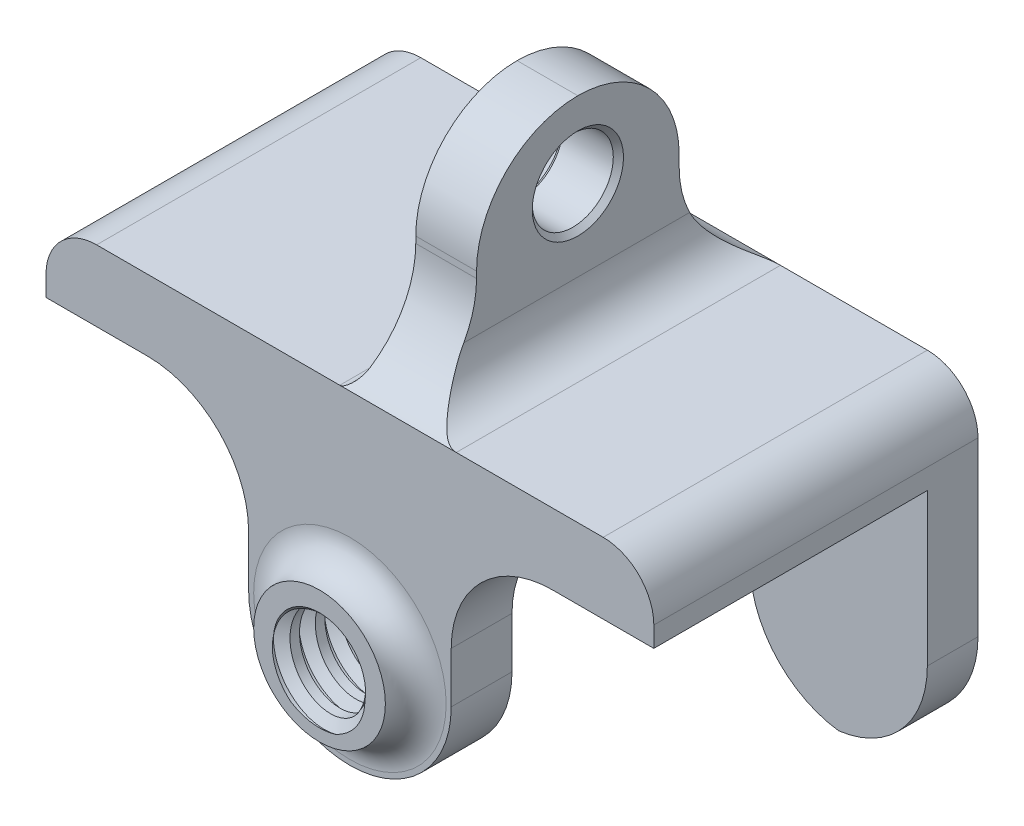
SolidWorks part; units mm, degrees
ref_plane "Front Plane" through (0, 0, 0) normal (0, 0, 1) x (1, 0, 0)
ref_plane "Top Plane" through (0, 0, 0) normal (0, 1, 0) x (1, 0, 0)
ref_plane "Right Plane" through (0, 0, 0) normal (1, 0, 0) x (0, 0, -1)
sketch "Sketch1" plane through (0, 0, 0) normal (1, 0, 0) x (0, 0, -1)
  line L0 (10.5, 0) -> (15.5, 0)
  line L2 (-10.5, 0) -> (-10.5, 25)
  line L3 (-10.5, 25) -> (10.5, 25)
  line L4 (10.5, 0) -> (10.5, 25)
  line L5 (-16.5, 0) -> (-10.5, 0)
  line L6 (-16.5, 0) -> (-16.5, 32)
  line L7 (-16.5, 32) -> (15.5, 32)
  line L8 (15.5, 0) -> (15.5, 32)
  point P4 (0, 25)
  dimension "D1" = 21
  dimension "D2" = 6
  dimension "D3" = 5
  dimension "D4" = 25
  dimension "D5" = 32
extrude "Boss-Extrude1" add sketch "Sketch1" along normal blind 60
ref_plane "Plane1" through (30, 0, 0) normal (-1, 0, 0) x (0, 0, 1)
sketch "Sketch2" plane through (0, 32, 0) normal (0, 1, 0) x (1, 0, 0)
  line L5 (30, 14.5945) -> (30, -14.5945) construction
  line L6 (36, 10) -> (30, 10)
  line L12 (36, 10) -> (36, -10)
  line L13 (36, -10) -> (30, -10)
  line L15 (30, 10) -> (30, -10)
  line L16 (36, 10) -> (30, -10) construction
  line L17 (36, -10) -> (30, 10) construction
  line L18 (-28.6, 0) -> (28.6, 0) construction
  point P0 (33, 0)
  dimension "D1" = 6
  dimension "D2" = 20
extrude "Boss-Extrude3" add sketch "Sketch2" along normal blind 20
fillet "Fillet1" radius 10 4 edges at (33, 32, -10) (33, 32, 10) (33, 52, 10) (33, 52, -10)
sketch "Sketch3" plane through (0, 0, 16.5) normal (0, 0, 1) x (1, 0, 0)
  line L0 (60, 0) -> (0, 0) construction
  line L1 (30, 14.5945) -> (30, -14.5945) construction
  point P0 (30, 10)
  dimension "D1" = 10
sketch "Sketch11" plane through (0, 0, 16.5) normal (0, 0, 1) x (1, 0, 0)
  circle A0 centre (30, 10) radius 6.5
  dimension "D1" = 13
extrude "Boss-Extrude4" add sketch "Sketch11" along normal blind 3
sketch "Sketch15" plane through (0, 0, 19.5) normal (0, 0, 1) x (1, 0, 0)
  circle A0 centre (30, 10) radius 3.75
  dimension "D1" = 7.5
extrude "Cut-Extrude3" cut sketch "Sketch15" against normal up to vertex (9 mm away) up to point (0, 0, 10.5)
chamfer "Chamfer3" distance 0.8 angle 45 2 edges at (33.75, 10, 10.5) (33.75, 10, 19.5)
sketch "Sketch16" plane through (0, 0, 19.5) normal (0, 0, 1) x (1, 0, 0)
  circle A0 centre (30, 10) radius 5
  dimension "D1" = 10
curve "Helix/Spiral2" pitch 2.5 height 13 turns 5.2
sketch "Sketch17" plane through (30, 0, 0) normal (1, 0, 0) x (0, 0, -1)
  line L4 (-20.6268, 15.3) -> (-20.9732, 15.3)
  line L5 (-20.9732, 15.3) -> (-22.1, 13.3483)
  line L7 (-22.1, 13.3483) -> (-19.5, 13.3483)
  line L8 (-19.5, 13.3483) -> (-20.6268, 15.3)
  line L9 (-20.6268, 15.3) -> (-20.8, 15.6) construction
  line L10 (-20.8, 15.6) -> (-20.9732, 15.3) construction
  line L11 (-19.5, 16.5) -> (-19.5, 3.5) construction
  dimension "D1" = 60
  dimension "D2" = 2.6
  dimension "D3" = 0.3
  dimension "D4" = 5.6
sweep "Cut-Sweep1" cut profiles "Sketch17" path "Helix/Spiral2"
hole_wizard "M10x1.5 Tapped Hole1" positions "Sketch4" profile "Sketch5" tap size "M10x1.5" standard "ANSI Metric" end condition up to next
sketch "Sketch4" plane through (0, 0, 19.5) normal (0, 0, 1) x (1, 0, 0)
  point P0 (30, 10)
sketch "Sketch5" plane through (30, 10, 19.5) normal (1, 0, 0) x (0, -1, 0)
  line L0 (0, 0) -> (0, 35)
  line L1 (0, 35) -> (4.25, 35)
  line L2 (4.25, 35) -> (4.25, 0)
  line L5 (4.25, 0) -> (0, 0)
  line L11 (0, -6.35) -> (0, 107.95) construction
  dimension "Thru Tap Drill Dia." = 8.5
  dimension "Thru Tap Drill Depth" = 35
cosmetic thread "Hole Thread7" parameters "D2"=10
fillet "Fillet7" radius 3 1 edges at (23.5, 10, 16.5)
sketch "Sketch6" plane through (36, 0, 0) normal (1, 0, 0) x (0, 0, -1)
  point P0 (0, 44.5)
  dimension "D1" = 7.5
hole_wizard "M8x1.25 Tapped Hole1" positions "Sketch7" profile "Sketch8" tap size "M8x1.25" standard "ANSI Metric" end condition through all
sketch "Sketch7" plane through (36, 0, 0) normal (1, 0, 0) x (0, 0, -1)
  point P0 (0, 44.5)
sketch "Sketch8" plane through (36, 44.5, 0) normal (0, 1, 0) x (0, 0, -1)
  line L0 (0, 0) -> (0, 36)
  line L1 (0, 36) -> (4, 36)
  line L2 (4, 36) -> (4, 0)
  line L5 (4, 0) -> (0, 0)
  line L11 (0, -6.35) -> (0, 107.95) construction
  dimension "Thread Major Dia." = 8
  dimension "Thru Tap Drill Depth" = 36
chamfer "Chamfer2" distance 0.5 angle 45 2 edges at (30, 44.5, -4) (36, 44.5, -4)
sketch "Sketch9" plane through (0, 0, 16.5) normal (0, 0, 1) x (1, 0, 0)
  line L1 (0, 0) -> (20, 0)
  line L2 (0, 0) -> (0, 25)
  line L3 (0, 25) -> (20, 25)
  line L4 (20, 0) -> (20, 25)
  line L5 (60, 0) -> (40, 0)
  line L6 (60, 0) -> (60, 25)
  line L7 (60, 25) -> (40, 25)
  line L8 (40, 0) -> (40, 25)
  dimension "D1" = 25
  dimension "D2" = 20
extrude "Cut-Extrude1" cut sketch "Sketch9" against normal up to vertex (6 mm away) up to point (0, 0, 10.5)
fillet "Fillet3" radius 10 4 edges at (40, 25, 13.5) (40, 0, 13.5) (20, 0, 13.5) (20, 25, 13.5)
sketch "Sketch10" plane through (0, 0, -15.5) normal (0, 0, -1) x (-1, 0, 0)
  line L0 (-60, 0) -> (0, 0) construction
  line L1 (-42.5, 0) -> (-17.5, 0)
  line L2 (-42.5, 0) -> (-42.5, 25)
  line L3 (-42.5, 25) -> (-17.5, 25)
  line L4 (-17.5, 0) -> (-17.5, 25)
  line L5 (-30, -14.5945) -> (-30, 14.5945) construction
  point P6 (-30, 25)
  dimension "D1" = 25
  dimension "D2" = 25
extrude "Cut-Extrude2" cut sketch "Sketch10" against normal up to vertex (5 mm away) up to point (60, 0, -10.5)
fillet "Fillet4" radius 10 6 edges at (42.5, 25, -13) (0, 0, -13) (17.5, 25, -13) (42.5, 0, -13) (60, 0, -13) (17.5, 0, -13)
fillet "Fillet5" radius 5 2 edges at (60, 32, 0.5) (0, 32, 0.5)
fillet "Fillet6" radius 1 1 edges at (30, 32, 0.5)
fillet "Fillet8" radius 4.5 1 edges at (36, 32, 0.5)
